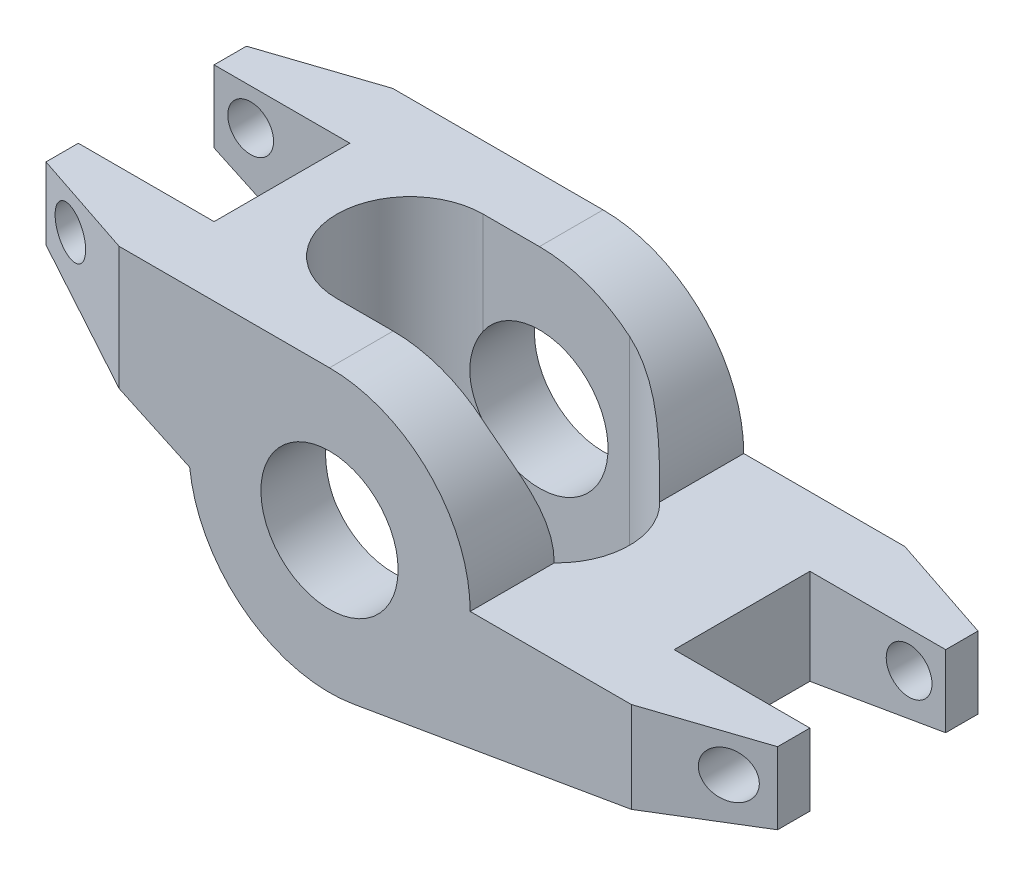
SolidWorks part; units mm, degrees
ref_plane "Front Plane" through (0, 0, 0) normal (0, 0, 1) x (1, 0, 0)
ref_plane "Top Plane" through (0, 0, 0) normal (0, 1, 0) x (1, 0, 0)
ref_plane "Right Plane" through (0, 0, 0) normal (1, 0, 0) x (0, 0, -1)
sketch "Sketch1" plane through (0, 0, 0) normal (0, 0, 1) x (1, 0, 0)
  line L0 (0, 9.77) -> (-22.23, 9.77)
  line L1 (-22.23, 9.77) -> (-22.23, 4.77)
  line L2 (-22.23, 4.77) -> (-9.7115, -1.0675)
  line L3 (9.77, 0) -> (28.58, 0)
  line L4 (28.58, 0) -> (28.58, -5)
  line L5 (28.58, -5) -> (1.6553, -9.6287)
  arc A0 (-9.7115, -1.0675) -> (1.6553, -9.6287) centre (0, 0) ccw
  circle A1 centre (0, 0) radius 4.765
  arc A2 (9.77, 0) -> (0, 9.77) centre (0, 0) ccw
  dimension "D1" = 19.54
  dimension "D2" = 9.53
  dimension "D3" = 22.23
  dimension "D4" = 5
  dimension "D5" = 25
  dimension "D6" = 5
  dimension "D7" = 28.58
extrude "Boss-Extrude1" add sketch "Sketch1" along normal mid plane 19
sketch "Sketch3" plane through (0, 9.77, 0) normal (0, 1, 0) x (1, 0, 0)
  line L0 (-22.23, -9.5) -> (-22.23, 9.5) construction
  line L1 (-22.23, -4.715) -> (-12.8, -4.715)
  line L2 (-22.23, -4.715) -> (-22.23, 4.715)
  line L3 (-22.23, 4.715) -> (-12.8, 4.715)
  line L4 (-12.8, -4.715) -> (-12.8, 4.715)
  line L5 (28.58, -9.5) -> (28.58, 9.5) construction
  line L6 (28.58, -4.715) -> (19.15, -4.715)
  line L7 (28.58, -4.715) -> (28.58, 4.715)
  line L8 (28.58, 4.715) -> (19.15, 4.715)
  line L9 (19.15, -4.715) -> (19.15, 4.715)
  point P12 (-22.23, 0)
  point P14 (19.15, 0)
  dimension "D1" = 9.43
extrude "Cut-Extrude1" cut sketch "Sketch3" against normal through all
sketch "Sketch4" plane through (0, 9.77, 0) normal (0, 1, 0) x (1, 0, 0)
  line L0 (-3.91, 0) -> (6.25, 0) construction
  line L1 (-3.91, 5.08) -> (6.25, 5.08)
  line L2 (-3.91, -5.08) -> (6.25, -5.08)
  line L3 (-12.8, -4.715) -> (-12.8, 4.715) construction
  arc A0 (-3.91, 5.08) -> (-3.91, -5.08) centre (-3.91, 0) ccw
  arc A1 (6.25, -5.08) -> (6.25, 5.08) centre (6.25, 0) ccw
  point P3 (1.17, 0)
  dimension "D3" = 5.08
  dimension "D1" = 8.89
  dimension "D2" = 10.16
extrude "Cut-Extrude2" cut sketch "Sketch4" against normal through all
sketch "Sketch5" plane through (0, 0, 9.5) normal (0, 0, 1) x (1, 0, 0)
  line L0 (0, 9.77) -> (-22.23, 9.77) construction
  line L1 (-22.23, 9.77) -> (-22.23, 4.77) construction
  line L2 (28.58, -5) -> (28.58, 0) construction
  line L3 (28.58, 0) -> (9.77, 0) construction
  circle A0 centre (-19.69, 7.23) radius 1.59
  circle A1 centre (26.04, -2.54) radius 1.59
  point P8 (-20.254, 6.7097)
  dimension "D1" = 3.18
  dimension "D2" = 2.54
  dimension "D3" = 2.54
  dimension "D4" = 2.54
  dimension "D5" = 2.54
extrude "Cut-Extrude3" cut sketch "Sketch5" against normal through all
chamfer "Chamfer1" distance 7.62 distance2 2.54 2 edges at (28.58, -2.5, -9.5) (-22.23, 7.27, -9.5) first distance on face at (-18.1, 7.23, -9.5)
chamfer "Chamfer2" distance 2.54 distance2 7.62 2 edges at (28.58, -2.5, 9.5) (-22.23, 7.27, 9.5) first distance on face at (28.58, -2.5, 7.1075) first distance on face at (-22.23, 7.27, 7.1075)
